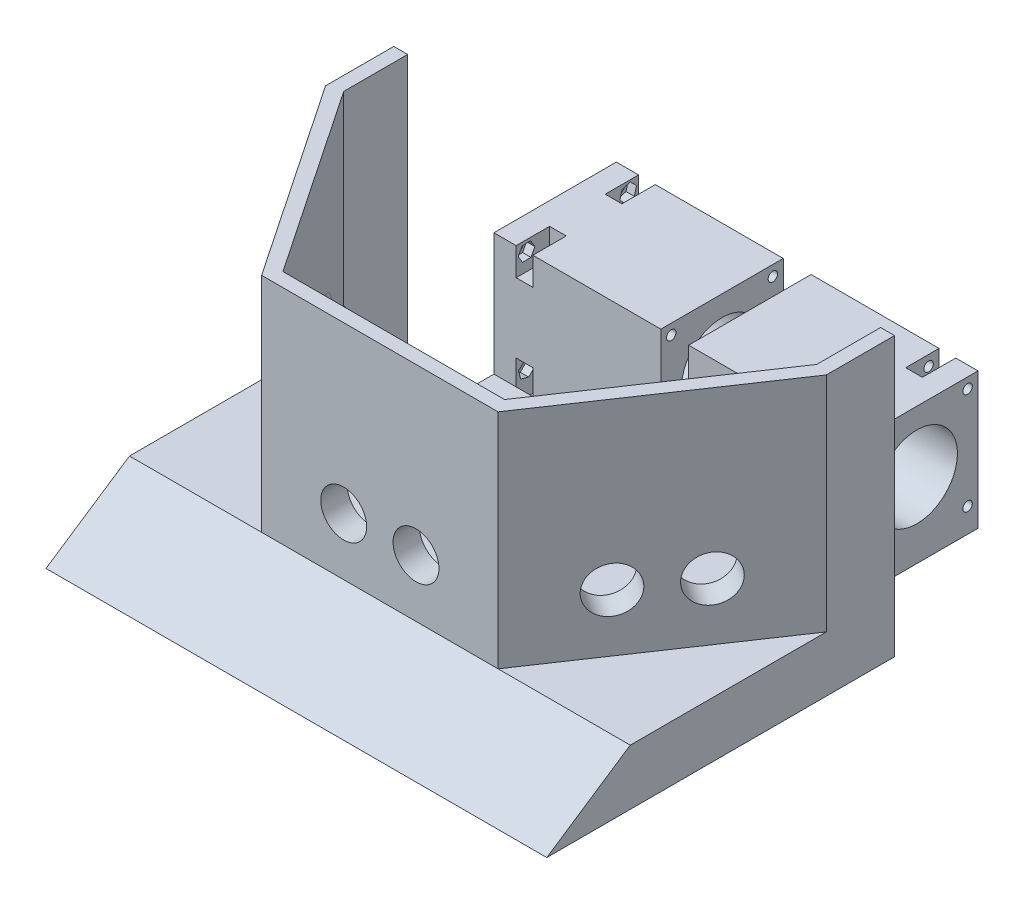
SolidWorks part; units mm, degrees
other "Markup1"
sketch "Sketch35"
ref_plane "Front Plane" through (0, 0, 0) normal (0, 0, 1) x (1, 0, 0)
ref_plane "Top Plane" through (0, 0, 0) normal (0, 1, 0) x (1, 0, 0)
ref_plane "Right Plane" through (0, 0, 0) normal (1, 0, 0) x (0, 0, -1)
sketch "Sketch1" plane through (0, 0, 0) normal (0, 0, 1) x (1, 0, 0)
  line L1 (-76.9072, 53.1959) -> (103.0928, 53.1959)
  line L2 (-76.9072, 53.1959) -> (-76.9072, -46.8041)
  line L3 (-76.9072, -46.8041) -> (103.0928, -46.8041)
  line L4 (103.0928, 53.1959) -> (103.0928, -46.8041)
  dimension "D1" = 180
  dimension "D2" = 100
extrude "Boss-Extrude1" add sketch "Sketch1" along normal blind 150
sketch "Sketch2" plane through (0, 53.1959, 0) normal (0, 1, 0) x (1, 0, 0)
  line L0 (13.0928, 0) -> (13.0928, -150) construction
  line L4 (103.0928, 0) -> (-76.9072, 0) construction
  line L9 (103.0928, -150) -> (-76.9072, -150) construction
sketch "Sketch4" plane through (0, 53.1959, 0) normal (0, 1, 0) x (1, 0, 0)
  line L0 (-29.4072, -150) -> (55.5928, -150) construction
  line L1 (-76.9072, 0) -> (-76.9072, -79.5106) construction
  line L3 (-76.9072, -150) -> (-76.9072, 0) construction
  line L5 (-76.9072, -79.5106) -> (-29.4072, -150) construction
  line L6 (13.0928, 0) -> (13.0928, -150) construction
  line L8 (103.0928, -150) -> (-76.9072, -150) construction
  line L9 (103.0928, 0) -> (103.0928, -79.5106) construction
  line L10 (103.0928, -150) -> (103.0928, 0) construction
  line L11 (103.0928, -79.5106) -> (55.5928, -150) construction
  line L13 (-76.9072, -79.5106) -> (-29.4072, -150)
  line L14 (-29.4072, -150) -> (-76.9072, -150)
  line L15 (-76.9072, -150) -> (-76.9072, -79.5106)
  line L16 (55.5928, -150) -> (103.0928, -150)
  line L17 (103.0928, -150) -> (103.0928, -79.5106)
  line L18 (103.0928, -79.5106) -> (55.5928, -150)
  dimension "D1" = 85
  dimension "D2" = 47.5
  dimension "D3" = 47.5
  dimension "D4" = 85
  dimension "D5" = 79.5106
extrude "Cut-Extrude2" cut sketch "Sketch4" against normal blind 80
shell "Shell1" thickness 5 removed face at (13.0928, 53.1959, 76.5035)
sketch "Sketch6" plane through (103.0928, 0, 0) normal (1, 0, 0) x (0, 0, -1)
  line L0 (-150, -26.8041) -> (-150, -46.8041)
  line L1 (-150, -46.8041) -> (-180, -46.8041)
  line L2 (-180, -46.8041) -> (-150, -26.8041)
  dimension "D1" = 30
  dimension "D2" = 36.0555
extrude "Boss-Extrude2" add sketch "Sketch6" against normal blind 180 contours L2 L0 L1
sketch "Sketch26" plane through (0, 0, 0) normal (0, 0, -1) x (-1, 0, 0)
  line L0 (76.9072, 53.1959) -> (76.9072, -46.8041) construction
  line L1 (-103.0928, 53.1959) -> (76.9072, 53.1959)
  line L2 (-103.0928, 53.1959) -> (-103.0928, -41.8041)
  line L3 (-103.0928, -41.8041) -> (76.9072, -41.8041)
  line L4 (76.9072, 53.1959) -> (76.9072, -41.8041)
  dimension "D1" = 95
extrude "Cut-Extrude10" cut sketch "Sketch26" against normal blind 5
sketch "Sketch27" plane through (103.0928, 0, 0) normal (1, 0, 0) x (0, 0, -1)
  line L1 (-5, 53.1959) -> (-55, 53.1959)
  line L2 (-5, 53.1959) -> (-5, -41.8041)
  line L3 (-5, -41.8041) -> (-55, -41.8041)
  line L4 (-55, 53.1959) -> (-55, -41.8041)
  dimension "D1" = 50
  dimension "D2" = 95
extrude "Cut-Extrude11" cut sketch "Sketch27" against normal through all
sketch3d "3DSketch1" plane through (0, 0, 0) normal (0, 0, 1) x (1, 0, 0)
sketch "Sketch28" plane through (-89.7376, 0, 60.4706) normal (-0.8293, 0, 0.5588) x (0.5588, 0, 0.8293)
  line L0 (22.9595, -26.8041) -> (107.9595, -26.8041) construction
  line L1 (107.9595, -26.8041) -> (107.9595, 53.1959) construction
  line L2 (22.9595, -26.8041) -> (22.9595, 53.1959) construction
  circle A0 centre (52.4595, -6.2041) radius 8.25
  circle A1 centre (78.4595, -6.2041) radius 8.25
  dimension "D1" = 16.5
  dimension "D2" = 16.5
  dimension "D3" = 26
  dimension "D4" = 20.6
  dimension "D5" = 29.5
  dimension "D6" = 29.5
extrude "Cut-Extrude12" cut sketch "Sketch28" against normal blind 82
sketch "Sketch29" plane through (107.7458, 0, 72.6056) normal (0.8293, 0, 0.5588) x (0.5588, 0, -0.8293)
  line L0 (-8.3264, -26.8041) -> (-8.3264, 53.1959) construction
  line L2 (-8.3264, -26.8041) -> (-93.3264, -26.8041) construction
  circle A0 centre (-63.8264, -6.2041) radius 8.25
  circle A1 centre (-37.8264, -6.2041) radius 8.25
  dimension "D1" = 16.5
  dimension "D2" = 16.5
  dimension "D3" = 26
  dimension "D4" = 29.5
  dimension "D5" = 20.6
  dimension "D6" = 20.6
extrude "Cut-Extrude13" cut sketch "Sketch29" against normal blind 82
sketch "Sketch30" plane through (0, 0, 150) normal (0, 0, 1) x (1, 0, 0)
  line L0 (-29.4072, -26.8041) -> (55.5928, -26.8041) construction
  line L1 (55.5928, -26.8041) -> (55.5928, 53.1959) construction
  line L2 (-29.4072, -26.8041) -> (-29.4072, 53.1959) construction
  circle A0 centre (0.0928, -6.2041) radius 8.25
  circle A1 centre (26.0928, -6.2041) radius 8.25
  dimension "D1" = 16.5
  dimension "D2" = 16.5
  dimension "D4" = 20.6
  dimension "D3" = 26
  dimension "D5" = 20.6
  dimension "D6" = 29.5
  dimension "D7" = 29.5
extrude "Cut-Extrude14" cut sketch "Sketch30" against normal blind 82 contours A0 | A1
sketch "Sketch31" plane through (103.5994, 0, 69.8115) normal (-0.8293, 0, -0.5588) x (-0.5588, 0, 0.8293)
  circle A1 centre (63.8264, -6.2041) radius 10.25
  circle A2 centre (63.8264, -6.2041) radius 8.25 construction
  circle A3 centre (37.8264, -6.2041) radius 10.25
  circle A4 centre (37.8264, -6.2041) radius 8.25 construction
  circle A5 centre (63.8264, -6.2041) radius 8.25
  circle A6 centre (37.8264, -6.2041) radius 8.25
  dimension "D1" = 2
  dimension "D2" = 2
extrude "Boss-Extrude4" add sketch "Sketch31" along normal blind 4.5
sketch "Sketch33" plane through (0, 0, 145) normal (0, 0, -1) x (-1, 0, 0)
  circle A0 centre (-26.0928, -6.2041) radius 8.25
  circle A1 centre (-26.0928, -6.2041) radius 10.25
  circle A2 centre (-0.0928, -6.2041) radius 8.25
  circle A3 centre (-0.0928, -6.2041) radius 10.25
  dimension "D1" = 2
  dimension "D2" = 2
extrude "Boss-Extrude5" add sketch "Sketch33" along normal blind 4.5
sketch "Sketch34" plane through (-85.5911, 0, 57.6765) normal (0.8293, 0, -0.5588) x (-0.5588, 0, -0.8293)
  circle A0 centre (-78.4595, -6.2041) radius 8.25
  circle A1 centre (-52.4595, -6.2041) radius 8.25
  circle A2 centre (-78.4595, -6.2041) radius 10.25
  circle A3 centre (-52.4595, -6.2041) radius 10.25
  dimension "D1" = 2
  dimension "D2" = 2
extrude "Boss-Extrude6" add sketch "Sketch34" along normal blind 4.5
fillet "Fillet1" radius 3 6 edges at (-50.5475, -6.2041, 109.6807) (-36.0181, -6.2041, 131.2421) (10.3428, -6.2041, 145) (36.3428, -6.2041, 145) (76.7331, -6.2041, 109.6807) (62.2037, -6.2041, 131.2421)
sketch "Sketch36" plane through (0, -41.8041, 0) normal (0, 1, 0) x (1, 0, 0)
  line L0 (13.0928, 0) -> (8.0928, 0) construction
  line L1 (103.0928, 0) -> (-76.9072, 0) construction
  line L2 (13.0928, 0) -> (18.0928, 0) construction
  line L8 (8.0928, 0) -> (-51.9072, 0) construction
  line L9 (18.0928, 0) -> (78.0928, 0) construction
  line L10 (-51.9072, 0) -> (8.0928, 0)
  line L11 (-51.9072, 0) -> (-51.9072, -44)
  line L12 (-51.9072, -44) -> (8.0928, -44)
  line L13 (8.0928, 0) -> (8.0928, -44)
  line L15 (18.0928, 0) -> (78.0928, 0)
  line L16 (18.0928, 0) -> (18.0928, -44)
  line L17 (18.0928, -44) -> (78.0928, -44)
  line L18 (78.0928, 0) -> (78.0928, -44)
  dimension "D1" = 5
  dimension "D2" = 5
  dimension "D3" = 44
  dimension "D4" = 60
  dimension "D5" = 60
  dimension "D6" = 44
extrude "Boss-Extrude7" add sketch "Sketch36" along normal blind 44
sketch "Sketch37" plane through (-51.9072, 0, 0) normal (-1, 0, 0) x (0, 0, 1)
  line L0 (22, 2.1959) -> (22, -41.8041) construction
  line L1 (0, 2.1959) -> (44, 2.1959) construction
  line L2 (0, -41.8041) -> (44, -41.8041) construction
  line L3 (0, -19.8041) -> (44, -19.8041) construction
  line L4 (0, 2.1959) -> (0, -41.8041) construction
  line L5 (44, 2.1959) -> (44, -41.8041) construction
  circle A0 centre (22, -19.8041) radius 14.6
  dimension "D1" = 29.2
extrude "Cut-Extrude15" cut sketch "Sketch37" against normal blind 146
sketch "Sketch42" plane through (78.0928, 0, 0) normal (1, 0, 0) x (0, 0, -1)
  line L0 (-44, 2.1959) -> (0, 2.1959) construction
  line L1 (0, 2.1959) -> (0, -41.8041) construction
  line L2 (-44, 2.1959) -> (-44, -41.8041) construction
  line L3 (-44, -41.8041) -> (0, -41.8041) construction
  circle A1 centre (-3.74, -1.5441) radius 1.6875
  circle A2 centre (-3.74, -38.0641) radius 1.6875
  circle A3 centre (-40.26, -38.0641) radius 1.6875
  circle A5 centre (-40.26, -1.5441) radius 1.6875
  dimension "D2" = 3.375
  dimension "D3" = 3.375
  dimension "D4" = 3.375
  dimension "D14" = 3.375
  dimension "D5" = 3.74
  dimension "D6" = 3.74
  dimension "D8" = 3.74
  dimension "D9" = 3.74
  dimension "D10" = 3.74
  dimension "D11" = 3.74
  dimension "D12" = 3.74
  dimension "D13" = 3.74
extrude "Cut-Extrude19" cut sketch "Sketch42" against normal blind 179.1
sketch "Sketch43" plane through (0, -41.8041, 0) normal (0, 1, 0) x (1, 0, 0)
  line L1 (78.0928, 0) -> (103.0928, 0)
  line L2 (78.0928, 0) -> (78.0928, -55)
  line L3 (78.0928, -55) -> (103.0928, -55)
  line L4 (103.0928, 0) -> (103.0928, -55)
  line L5 (-51.9072, 0) -> (-76.9072, 0)
  line L6 (-51.9072, 0) -> (-51.9072, -55)
  line L7 (-51.9072, -55) -> (-76.9072, -55)
  line L8 (-76.9072, 0) -> (-76.9072, -55)
extrude "Cut-Extrude20" cut sketch "Sketch43" against normal blind 6.2
sketch "Sketch47" plane through (0, 2.1959, 0) normal (0, 1, 0) x (1, 0, 0)
  line L0 (8.0928, 0) -> (-51.9072, 0) construction
  line L1 (-43.9072, 0) -> (-37.9072, 0)
  line L2 (-43.9072, 0) -> (-43.9072, -12)
  line L3 (-43.9072, -12) -> (-37.9072, -12)
  line L4 (-37.9072, 0) -> (-37.9072, -12)
  line L5 (-51.9072, -44) -> (8.0928, -44) construction
  line L6 (-43.9072, -44) -> (-37.9072, -44)
  line L7 (-43.9072, -44) -> (-43.9072, -32)
  line L8 (-43.9072, -32) -> (-37.9072, -32)
  line L9 (-37.9072, -44) -> (-37.9072, -32)
  line L10 (18.0928, -44) -> (78.0928, -44) construction
  line L19 (70.0928, -44) -> (64.0928, -44)
  line L20 (70.0928, -44) -> (70.0928, -32)
  line L21 (70.0928, -32) -> (64.0928, -32)
  line L22 (64.0928, -44) -> (64.0928, -32)
  line L23 (78.0928, 0) -> (18.0928, 0) construction
  line L24 (70.0928, 0) -> (64.0928, 0)
  line L25 (70.0928, 0) -> (70.0928, -12)
  line L26 (70.0928, -12) -> (64.0928, -12)
  line L27 (64.0928, 0) -> (64.0928, -12)
  dimension "D2" = 8
  dimension "D3" = 8
  dimension "D4" = 8
  dimension "D5" = 8
  dimension "D6" = 12
  dimension "D7" = 12
  dimension "D8" = 12
  dimension "D9" = 12
  dimension "D10" = 6
  dimension "D11" = 6
  dimension "D12" = 6
  dimension "D13" = 6
extrude "Cut-Extrude24" cut sketch "Sketch47" against normal blind 10
sketch "Sketch55" plane through (0, -46.8041, 0) normal (0, -1, 0) x (1, 0, 0)
  line L0 (78.0928, 44) -> (-51.9072, 44) construction
  line L1 (78.0928, 0) -> (78.0928, 55) construction
  line L2 (-51.9072, 55) -> (-51.9072, 0) construction
  line L3 (-51.9072, 0) -> (78.0928, 0) construction
  line L4 (70.0928, 44) -> (64.0928, 44)
  line L5 (70.0928, 44) -> (70.0928, 32)
  line L6 (70.0928, 32) -> (64.0928, 32)
  line L7 (64.0928, 44) -> (64.0928, 32)
  line L8 (70.0928, 0) -> (64.0928, 0)
  line L9 (70.0928, 0) -> (70.0928, 12)
  line L10 (70.0928, 12) -> (64.0928, 12)
  line L11 (64.0928, 0) -> (64.0928, 12)
  line L13 (-37.9072, 44) -> (-43.9072, 44)
  line L14 (-37.9072, 44) -> (-37.9072, 32)
  line L15 (-37.9072, 32) -> (-43.9072, 32)
  line L16 (-43.9072, 44) -> (-43.9072, 32)
  line L17 (-37.9072, 0) -> (-43.9072, 0)
  line L18 (-37.9072, 0) -> (-37.9072, 12)
  line L19 (-37.9072, 12) -> (-43.9072, 12)
  line L20 (-43.9072, 0) -> (-43.9072, 12)
  dimension "D1" = 11
  dimension "D2" = 11
  dimension "D3" = 8
  dimension "D4" = 8
  dimension "D5" = 6
  dimension "D6" = 6
  dimension "D7" = 12
  dimension "D8" = 12
  dimension "D9" = 8
  dimension "D10" = 8
  dimension "D11" = 12
  dimension "D12" = 12
  dimension "D13" = 6
  dimension "D14" = 6
extrude "Cut-Extrude31" cut sketch "Sketch55" against normal blind 14
sketch "Sketch63" plane through (70.0928, 0, 0) normal (-1, 0, 0) x (0, 0, 1)
  line L1 (6.74, -1.5215) -> (5.2204, 1.0653)
  line L2 (5.2204, 1.0653) -> (2.2204, 1.0426)
  line L3 (2.2204, 1.0426) -> (0.74, -1.5668)
  line L4 (0.74, -1.5668) -> (2.2596, -4.1535)
  line L5 (2.2596, -4.1535) -> (5.2596, -4.1309)
  line L6 (5.2596, -4.1309) -> (6.74, -1.5215)
  line L7 (43.2365, -1.9192) -> (42.0731, 0.846)
  line L8 (42.0731, 0.846) -> (39.0966, 1.2211)
  line L9 (39.0966, 1.2211) -> (37.2835, -1.1691)
  line L10 (37.2835, -1.1691) -> (38.4469, -3.9343)
  line L11 (38.4469, -3.9343) -> (41.4234, -4.3094)
  line L12 (41.4234, -4.3094) -> (43.2365, -1.9192)
  circle A0 centre (3.74, -1.5441) radius 2.5982 construction
  circle A1 centre (40.26, -1.5441) radius 2.5981 construction
  dimension "D1" = 6
  dimension "D2" = 6
extrude "Cut-Extrude36" cut sketch "Sketch63" against normal blind 3
sketch "Sketch64" plane through (70.0928, 0, 0) normal (-1, 0, 0) x (0, 0, 1)
  line L1 (6.74, -38.0641) -> (5.24, -35.466)
  line L2 (5.24, -35.466) -> (2.24, -35.466)
  line L3 (2.24, -35.466) -> (0.74, -38.0641)
  line L4 (0.74, -38.0641) -> (2.24, -40.6622)
  line L5 (2.24, -40.6622) -> (5.24, -40.6622)
  line L6 (5.24, -40.6622) -> (6.74, -38.0641)
  line L7 (43.26, -38.0641) -> (41.76, -35.466)
  line L8 (41.76, -35.466) -> (38.76, -35.466)
  line L9 (38.76, -35.466) -> (37.26, -38.0641)
  line L10 (37.26, -38.0641) -> (38.76, -40.6622)
  line L11 (38.76, -40.6622) -> (41.76, -40.6622)
  line L12 (41.76, -40.6622) -> (43.26, -38.0641)
  circle A0 centre (3.74, -38.0641) radius 2.5981 construction
  circle A1 centre (40.26, -38.0641) radius 2.5981 construction
  dimension "D1" = 6
  dimension "D2" = 6
extrude "Cut-Extrude37" cut sketch "Sketch64" against normal blind 3
sketch "Sketch65" plane through (-43.9072, 0, 0) normal (1, 0, 0) x (0, 0, -1)
  line L1 (-2.9576, 1.4682) -> (-5.9576, 0.6397)
  line L2 (-5.9576, 0.6397) -> (-6.74, -2.3727)
  line L3 (-6.74, -2.3727) -> (-4.5224, -4.5565)
  line L4 (-4.5224, -4.5565) -> (-1.5224, -3.7279)
  line L5 (-1.5224, -3.7279) -> (-0.74, -0.7155)
  line L6 (-0.74, -0.7155) -> (-2.9576, 1.4682)
  line L7 (-38.8262, 1.0911) -> (-41.8252, 1.0152)
  line L8 (-41.8252, 1.0152) -> (-43.259, -1.62)
  line L9 (-43.259, -1.62) -> (-41.6938, -4.1793)
  line L10 (-41.6938, -4.1793) -> (-38.6948, -4.1034)
  line L11 (-38.6948, -4.1034) -> (-37.261, -1.4683)
  line L12 (-37.261, -1.4683) -> (-38.8262, 1.0911)
  circle A0 centre (-3.74, -1.5441) radius 2.6954 construction
  circle A1 centre (-40.26, -1.5441) radius 2.5981 construction
  dimension "D1" = 6
  dimension "D2" = 6
extrude "Cut-Extrude38" cut sketch "Sketch65" against normal blind 3
sketch "Sketch66" plane through (-43.9072, 0, 0) normal (1, 0, 0) x (0, 0, -1)
  line L1 (-0.74, -38.42) -> (-1.9318, -35.644)
  line L2 (-1.9318, -35.644) -> (-4.9318, -35.2881)
  line L3 (-4.9318, -35.2881) -> (-6.74, -37.7082)
  line L4 (-6.74, -37.7082) -> (-5.5482, -40.4843)
  line L5 (-5.5482, -40.4843) -> (-2.5482, -40.8401)
  line L6 (-2.5482, -40.8401) -> (-0.74, -38.42)
  line L7 (-39.5254, -40.9728) -> (-37.3737, -38.8823)
  line L8 (-37.3737, -38.8823) -> (-38.1083, -35.9736)
  line L9 (-38.1083, -35.9736) -> (-40.9946, -35.1554)
  line L10 (-40.9946, -35.1554) -> (-43.1463, -37.2459)
  line L11 (-43.1463, -37.2459) -> (-42.4117, -40.1546)
  line L12 (-42.4117, -40.1546) -> (-39.5254, -40.9728)
  circle A0 centre (-3.74, -38.0641) radius 2.6163 construction
  circle A1 centre (-40.26, -38.0641) radius 2.5981 construction
  dimension "D1" = 6
  dimension "D2" = 6
extrude "Cut-Extrude39" cut sketch "Sketch66" against normal blind 3
